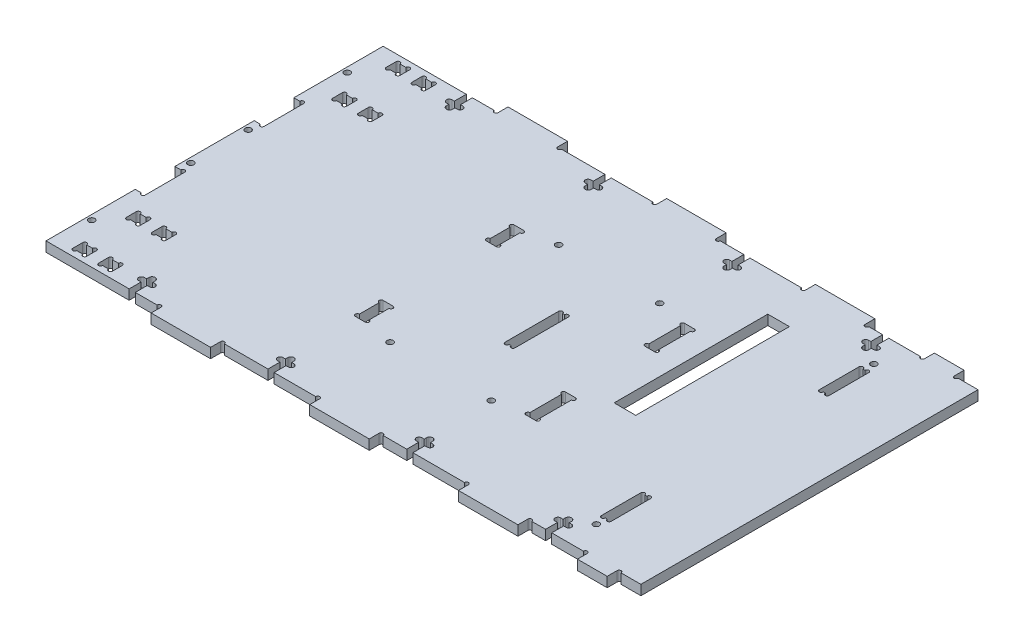
SolidWorks part; units mm, degrees
ref_plane "정면" through (0, 0, 0) normal (0, 0, 1) x (1, 0, 0)
ref_plane "윗면" through (0, 0, 0) normal (0, 1, 0) x (1, 0, 0)
ref_plane "우측면" through (0, 0, 0) normal (1, 0, 0) x (0, 0, -1)
sketch "스케치1" plane through (0, 0, 0) normal (0, 1, 0) x (1, 0, 0)
  line L1 (0, 0) -> (300, 0)
  line L2 (0, 0) -> (0, 170)
  line L3 (0, 170) -> (300, 170)
  line L4 (300, 0) -> (300, 170)
  dimension "D1" = 170
  dimension "D2" = 300
extrude "보스-돌출1" add sketch "스케치1" along normal blind 5
sketch "스케치2" plane through (0, 0, 0) normal (0, -1, 0) x (1, 0, 0)
  line L0 (160, -71.5) -> (160, 0) construction
  line L1 (160, -71.5) -> (165, -71.5)
  line L2 (160, -71.5) -> (160, -98.5)
  line L3 (160, -98.5) -> (165, -98.5)
  line L4 (165, -71.5) -> (165, -98.5)
  line L5 (0, 0) -> (300, 0) construction
  line L6 (160, -98.5) -> (160, -170) construction
  line L7 (300, -170) -> (0, -170) construction
  line L10 (300, 0) -> (300, -170) construction
  line L11 (260, 0) -> (260, -20) construction
  line L12 (260, -20) -> (265, -20)
  line L13 (260, -20) -> (260, -40)
  line L14 (260, -40) -> (265, -40)
  line L15 (265, -20) -> (265, -40)
  line L16 (260, -130) -> (265, -130)
  line L17 (260, -130) -> (260, -150)
  line L18 (260, -150) -> (265, -150)
  line L19 (265, -130) -> (265, -150)
  line L20 (260, -40) -> (260, -130) construction
  line L21 (260, -150) -> (260, -170) construction
  line L22 (265, -130) -> (265, -40) construction
  dimension "D1" = 27
  dimension "D2" = 140
  dimension "D3" = 5
  dimension "D4" = 20
  dimension "D5" = 20
  dimension "D6" = 40
  dimension "D7" = 5
extrude "컷-돌출1" cut sketch "스케치2" against normal blind 10
sketch "스케치3" plane through (0, 5, 0) normal (0, 1, 0) x (1, 0, 0)
  line L0 (183.55, 42.5) -> (180.45, 42.5) construction
  line L1 (183.55, 40) -> (183.55, 45) construction
  line L2 (180.45, 40) -> (180.45, 45) construction
  line L3 (180.45, 42.5) -> (132.55, 42.5) construction
  line L4 (132.55, 40) -> (132.55, 45) construction
  line L5 (132.55, 42.5) -> (129.45, 42.5) construction
  line L6 (129.45, 40) -> (129.45, 45) construction
  line L7 (183.55, 127.5) -> (180.45, 127.5) construction
  line L8 (183.55, 125) -> (183.55, 130) construction
  line L9 (180.45, 125) -> (180.45, 130) construction
  line L10 (180.45, 127.5) -> (132.55, 127.5) construction
  line L11 (132.55, 125) -> (132.55, 130) construction
  line L12 (132.55, 127.5) -> (129.45, 127.5) construction
  line L13 (129.45, 125) -> (129.45, 130) construction
  line L15 (2.5, 101) -> (2.5, 97.9) construction
  line L17 (5, 101) -> (0, 101) construction
  line L18 (262.5, 16.55) -> (262.5, 13.45) construction
  line L19 (265, 16.55) -> (260, 16.55) construction
  line L20 (265, 13.45) -> (260, 13.45) construction
  line L25 (262.5, 156.55) -> (262.5, 153.45) construction
  line L26 (265, 156.55) -> (260, 156.55) construction
  line L27 (265, 153.45) -> (260, 153.45) construction
  line L28 (5, 97.9) -> (0, 97.9) construction
  line L31 (2.5, 151) -> (2.5, 147.9) construction
  line L34 (2.5, 22.1) -> (2.5, 19) construction
  line L35 (5, 22.1) -> (0, 22.1) construction
  line L36 (5, 19) -> (0, 19) construction
  line L37 (2.5, 72.1) -> (2.5, 69) construction
  line L38 (5, 72.1) -> (0, 72.1) construction
  line L39 (5, 69) -> (0, 69) construction
  line L40 (5, 151) -> (0, 151) construction
  line L41 (5, 147.9) -> (0, 147.9) construction
  circle A0 centre (131, 127.5) radius 1.55
  circle A1 centre (182, 127.5) radius 1.55
  circle A2 centre (182, 42.5) radius 1.55
  circle A3 centre (131, 42.5) radius 1.55
  circle A4 centre (2.5, 70.55) radius 1.55
  circle A5 centre (2.5, 20.55) radius 1.55
  circle A6 centre (2.5, 99.45) radius 1.55
  circle A7 centre (2.5, 149.45) radius 1.55
  circle A8 centre (262.5, 155) radius 1.55
  circle A10 centre (262.5, 15) radius 1.55
  dimension "D1" = 3.1
extrude "컷-돌출2" cut sketch "스케치3" against normal blind 10
sketch "스케치4" plane through (0, 0, 0) normal (0, -1, 0) x (1, 0, 0)
  line L1 (0, -125) -> (5, -125)
  line L2 (0, -125) -> (0, -105)
  line L3 (0, -105) -> (5, -105)
  line L4 (5, -125) -> (5, -105)
  line L5 (0, -65) -> (5, -65)
  line L6 (0, -65) -> (0, -45)
  line L7 (0, -45) -> (5, -45)
  line L8 (5, -65) -> (5, -45)
extrude "컷-돌출3" cut sketch "스케치4" against normal blind 5
sketch "스케치5" plane through (0, 0, 0) normal (0, -1, 0) x (1, 0, 0)
  line L2 (5, -45) -> (0, -45) construction
  line L3 (0, -65) -> (5, -65) construction
  line L4 (5, -105) -> (0, -105) construction
  line L5 (0, -125) -> (5, -125) construction
  line L6 (160, -98.5) -> (165, -98.5) construction
  line L7 (165, -71.5) -> (160, -71.5) construction
  line L8 (265, -20) -> (260, -20) construction
  line L9 (260, -40) -> (265, -40) construction
  line L10 (265, -130) -> (260, -130) construction
  line L11 (260, -150) -> (265, -150) construction
  circle A1 centre (4, -45) radius 1
  circle A2 centre (4, -65) radius 1
  circle A5 centre (4, -105) radius 1
  circle A6 centre (4, -125) radius 1
  circle A8 centre (164, -98.5) radius 1
  circle A9 centre (161, -98.5) radius 1
  circle A10 centre (164, -71.5) radius 1
  circle A11 centre (161, -71.5) radius 1
  circle A12 centre (264, -20) radius 1
  circle A13 centre (261, -20) radius 1
  circle A14 centre (264, -40) radius 1
  circle A15 centre (261, -40) radius 1
  circle A16 centre (264, -130) radius 1
  circle A17 centre (261, -130) radius 1
  circle A18 centre (264, -150) radius 1
  circle A19 centre (261, -150) radius 1
  dimension "D1" = 2
extrude "컷-돌출4" cut sketch "스케치5" against normal blind 10
sketch "스케치8" plane through (0, 0, 0) normal (0, -1, 0) x (1, 0, 0)
  line L0 (0, 0) -> (300, 0) construction
  line L1 (58, 0) -> (88, 0)
  line L2 (58, 0) -> (58, 5)
  line L3 (58, 5) -> (88, 5)
  line L4 (88, 0) -> (88, 5)
  line L5 (0, 5) -> (58, 5) construction
  line L6 (0, 0) -> (300, 0) construction
  line L7 (138, 5) -> (168, 5)
  line L8 (138, 5) -> (138, 0)
  line L9 (138, 0) -> (168, 0)
  line L10 (168, 5) -> (168, 0)
  line L11 (0, 0) -> (300, 0) construction
  line L12 (213, 5) -> (243, 5)
  line L13 (213, 5) -> (213, 0)
  line L14 (213, 0) -> (243, 0)
  line L15 (243, 5) -> (243, 0)
  line L16 (0, 0) -> (300, 0) construction
  line L17 (273, 5) -> (288, 5)
  line L18 (273, 5) -> (273, 0)
  line L19 (273, 0) -> (288, 0)
  line L20 (288, 5) -> (288, 0)
  line L21 (300, 0) -> (300, -170) construction
  line L22 (0, -85) -> (300, -85) construction
  line L23 (0, -105) -> (0, -65) construction
  line L24 (288, -175) -> (288, -170)
  line L25 (273, -170) -> (288, -170)
  line L26 (273, -175) -> (273, -170)
  line L27 (273, -175) -> (288, -175)
  line L28 (243, -175) -> (243, -170)
  line L29 (213, -170) -> (243, -170)
  line L30 (213, -175) -> (213, -170)
  line L31 (213, -175) -> (243, -175)
  line L32 (168, -175) -> (168, -170)
  line L33 (138, -170) -> (168, -170)
  line L34 (138, -175) -> (138, -170)
  line L35 (138, -175) -> (168, -175)
  line L36 (88, -170) -> (88, -175)
  line L37 (58, -175) -> (88, -175)
  line L38 (58, -170) -> (58, -175)
  line L39 (58, -170) -> (88, -170)
  dimension "D1" = 12
  dimension "D2" = 15
  dimension "D3" = 30
  dimension "D4" = 30
  dimension "D5" = 45
  dimension "D6" = 30
  dimension "D7" = 50
  dimension "D8" = 30
extrude "보스-돌출2" add sketch "스케치8" against normal blind 5
sketch "스케치9" plane through (0, 0, 0) normal (0, -1, 0) x (1, 0, 0)
  line L0 (0, 0) -> (58, 0) construction
  line L1 (88, 0) -> (138, 0) construction
  line L2 (88, 0) -> (138, 0) construction
  line L3 (168, 0) -> (213, 0) construction
  line L4 (168, 0) -> (213, 0) construction
  line L5 (243, 0) -> (273, 0) construction
  line L6 (243, 0) -> (273, 0) construction
  line L7 (288, 0) -> (300, 0) construction
  line L8 (0, -85) -> (300, -85) construction
  line L9 (0, -105) -> (0, -65) construction
  line L10 (300, 0) -> (300, -170) construction
  circle A0 centre (57, 0) radius 1
  circle A1 centre (89, 0) radius 1
  circle A2 centre (137, 0) radius 1
  circle A3 centre (169, 0) radius 1
  circle A4 centre (212, 0) radius 1
  circle A5 centre (272, 0) radius 1
  circle A6 centre (244, 0) radius 1
  circle A7 centre (289, 0) radius 1
  circle A8 centre (289, -170) radius 1
  circle A9 centre (244, -170) radius 1
  circle A10 centre (272, -170) radius 1
  circle A11 centre (212, -170) radius 1
  circle A12 centre (169, -170) radius 1
  circle A13 centre (137, -170) radius 1
  circle A14 centre (89, -170) radius 1
  circle A15 centre (57, -170) radius 1
  dimension "D1" = 2
extrude "컷-돌출6" cut sketch "스케치9" against normal blind 5
sketch "스케치13" plane through (0, 5, 0) normal (0, 1, 0) x (1, 0, 0)
  line L0 (30, 8.5) -> (30, 30.5) construction
  line L1 (30, 8.5) -> (23, 8.5)
  line L2 (30, 8.5) -> (30, 3.5)
  line L3 (30, 3.5) -> (23, 3.5)
  line L4 (23, 8.5) -> (23, 3.5)
  line L5 (17, 8.5) -> (10, 8.5)
  line L6 (17, 8.5) -> (17, 3.5)
  line L7 (17, 3.5) -> (10, 3.5)
  line L8 (10, 8.5) -> (10, 3.5)
  line L9 (30, 19.5) -> (11.9274, 19.5) construction
  line L10 (10, 30.5) -> (10, 35.5)
  line L11 (17, 35.5) -> (10, 35.5)
  line L12 (17, 30.5) -> (17, 35.5)
  line L13 (17, 30.5) -> (10, 30.5)
  line L14 (23, 30.5) -> (23, 35.5)
  line L15 (30, 35.5) -> (23, 35.5)
  line L16 (30, 30.5) -> (30, 35.5)
  line L17 (30, 30.5) -> (23, 30.5)
  line L18 (0, 85) -> (49.672, 85) construction
  line L19 (0, 105) -> (0, 65) construction
  line L20 (30, 150.5) -> (11.9274, 150.5) construction
  line L21 (30, 161.5) -> (30, 139.5) construction
  line L22 (30, 139.5) -> (23, 139.5)
  line L23 (30, 139.5) -> (30, 134.5)
  line L24 (30, 134.5) -> (23, 134.5)
  line L25 (23, 139.5) -> (23, 134.5)
  line L26 (17, 139.5) -> (10, 139.5)
  line L27 (17, 139.5) -> (17, 134.5)
  line L28 (17, 134.5) -> (10, 134.5)
  line L29 (10, 139.5) -> (10, 134.5)
  line L30 (10, 161.5) -> (10, 166.5)
  line L31 (17, 166.5) -> (10, 166.5)
  line L32 (17, 161.5) -> (17, 166.5)
  line L33 (17, 161.5) -> (10, 161.5)
  line L34 (23, 161.5) -> (23, 166.5)
  line L35 (30, 166.5) -> (23, 166.5)
  line L36 (30, 161.5) -> (30, 166.5)
  line L37 (30, 161.5) -> (23, 161.5)
extrude "컷-돌출9" cut sketch "스케치13" against normal blind 10
sketch "스케치14" plane through (0, 0, 0) normal (0, -1, 0) x (1, 0, 0)
  line L0 (10, -8.5) -> (17, -8.5) construction
  line L1 (17, -3.5) -> (10, -3.5) construction
  line L2 (17, -30.5) -> (23, -30.5) construction
  line L3 (23, -30.5) -> (23, -8.5) construction
  line L4 (23, -8.5) -> (17, -8.5) construction
  line L5 (17, -8.5) -> (17, -30.5) construction
  line L6 (20, -30.5) -> (20, -8.5) construction
  line L7 (17, -19.5) -> (23, -19.5) construction
  line L8 (0, -85) -> (55.1733, -85) construction
  line L9 (0, -105) -> (0, -65) construction
  line L10 (17, -150.5) -> (23, -150.5) construction
  line L11 (20, -139.5) -> (20, -161.5) construction
  line L12 (17, -161.5) -> (17, -139.5) construction
  line L13 (23, -161.5) -> (17, -161.5) construction
  line L14 (23, -139.5) -> (23, -161.5) construction
  line L15 (17, -139.5) -> (23, -139.5) construction
  circle A0 centre (11, -8.5) radius 1
  circle A1 centre (11, -3.5) radius 1
  circle A2 centre (16, -3.5) radius 1
  circle A3 centre (16, -8.5) radius 1
  circle A4 centre (24, -8.5) radius 1
  circle A5 centre (24, -3.5) radius 1
  circle A6 centre (29, -3.5) radius 1
  circle A7 centre (29, -8.5) radius 1
  circle A8 centre (29, -30.5) radius 1
  circle A9 centre (29, -35.5) radius 1
  circle A10 centre (24, -35.5) radius 1
  circle A11 centre (24, -30.5) radius 1
  circle A12 centre (16, -30.5) radius 1
  circle A13 centre (16, -35.5) radius 1
  circle A14 centre (11, -35.5) radius 1
  circle A15 centre (11, -30.5) radius 1
  circle A16 centre (11, -139.5) radius 1
  circle A17 centre (11, -134.5) radius 1
  circle A18 centre (16, -134.5) radius 1
  circle A19 centre (16, -139.5) radius 1
  circle A20 centre (24, -139.5) radius 1
  circle A21 centre (24, -134.5) radius 1
  circle A22 centre (29, -134.5) radius 1
  circle A23 centre (29, -139.5) radius 1
  circle A24 centre (29, -161.5) radius 1
  circle A25 centre (29, -166.5) radius 1
  circle A26 centre (24, -166.5) radius 1
  circle A27 centre (24, -161.5) radius 1
  circle A28 centre (16, -161.5) radius 1
  circle A29 centre (16, -166.5) radius 1
  circle A30 centre (11, -166.5) radius 1
  circle A31 centre (11, -161.5) radius 1
  dimension "D1" = 2
extrude "컷-돌출10" cut sketch "스케치14" against normal blind 10
sketch "스케치15" plane through (0, 5, 0) normal (0, 1, 0) x (1, 0, 0)
  line L1 (111, 125) -> (116, 125)
  line L2 (111, 125) -> (111, 111)
  line L3 (111, 111) -> (116, 111)
  line L4 (116, 125) -> (116, 111)
  line L5 (111, 45) -> (116, 45)
  line L6 (111, 45) -> (111, 59)
  line L7 (111, 59) -> (116, 59)
  line L8 (116, 45) -> (116, 59)
  line L9 (197, 65) -> (202, 65)
  line L10 (197, 65) -> (197, 45)
  line L11 (197, 45) -> (202, 45)
  line L12 (202, 65) -> (202, 45)
  line L13 (197, 105) -> (202, 105)
  line L14 (197, 105) -> (197, 125)
  line L15 (197, 125) -> (202, 125)
  line L16 (202, 105) -> (202, 125)
  arc A0 (116, 56.5) -> (116, 59) centre (116, 57.75) ccw construction
  dimension "D1" = 5
extrude "컷-돌출11" cut sketch "스케치15" against normal blind 10
sketch "스케치16" plane through (0, 5, 0) normal (0, 1, 0) x (1, 0, 0)
  line L0 (111, 59) -> (111, 45) construction
  line L1 (116, 45) -> (116, 59) construction
  line L2 (111, 125) -> (111, 111) construction
  line L3 (116, 111) -> (116, 125) construction
  line L4 (202, 105) -> (202, 125) construction
  line L5 (197, 125) -> (197, 105) construction
  line L6 (197, 65) -> (197, 45) construction
  line L7 (202, 45) -> (202, 65) construction
  circle A0 centre (111, 46) radius 1
  circle A1 centre (116, 46) radius 1
  circle A2 centre (116, 58) radius 1
  circle A3 centre (111, 58) radius 1
  circle A4 centre (111, 112) radius 1
  circle A5 centre (116, 112) radius 1
  circle A6 centre (116, 124) radius 1
  circle A7 centre (111, 124) radius 1
  circle A8 centre (202, 124) radius 1
  circle A10 centre (197, 124) radius 1
  circle A11 centre (197, 64) radius 1
  circle A12 centre (202, 64) radius 1
  circle A13 centre (202, 106) radius 1
  circle A14 centre (197, 106) radius 1
  circle A15 centre (197, 46) radius 1
  circle A16 centre (202, 46) radius 1
  dimension "D1" = 2
extrude "컷-돌출12" cut sketch "스케치16" against normal blind 10
sketch "스케치17" plane through (0, 5, 0) normal (0, 1, 0) x (1, 0, 0)
  line L0 (219, 97.5569) -> (219, 95.1974) construction
  line L1 (214, 72.5) -> (224.9, 72.5)
  line L2 (214, 72.5) -> (214, 150)
  line L3 (214, 150) -> (224.9, 150)
  line L4 (224.9, 72.5) -> (224.9, 150)
  line L6 (219.9, 97.5569) -> (219.9, 95.1974) construction
  line L7 (2.5, -7.5) -> (297.5, -7.5) construction
  line L8 (211, 170) -> (170, 170) construction
  dimension "D1" = 5
  dimension "D2" = 5
  dimension "D3" = 80
  dimension "D4" = 20
extrude "컷-돌출13" cut sketch "스케치17" against normal blind 10
sketch "스케치7" plane through (0, 0, 0) normal (0, -1, 0) x (1, 0, 0)
  line L0 (115.0287, -170) -> (111.9287, -170)
  line L1 (115.0287, -164) -> (116.2287, -164)
  line L2 (115.0287, -161.2) -> (115.0287, -160)
  line L3 (111.9287, -161.2) -> (111.9287, -160)
  line L4 (111.9287, -161.2) -> (110.7287, -161.2)
  line L5 (111.9287, -170) -> (111.9287, -164)
  line L6 (110.7287, -164) -> (111.9287, -164)
  line L7 (115.0287, -170) -> (115.0287, -164)
  line L8 (116.2287, -161.2) -> (115.0287, -161.2)
  line L9 (115.0287, -161.2) -> (111.9287, -161.2) construction
  line L10 (115.0287, -161.2) -> (115.0287, -164) construction
  line L11 (111.9287, -164) -> (111.9287, -161.2) construction
  line L12 (115.0287, -160) -> (111.9287, -160) construction
  line L13 (113.4787, -160) -> (113.4787, -157.529) construction
  line L14 (110.7287, -161.2) -> (110.7287, -164) construction
  line L15 (116.2287, -164) -> (116.2287, -161.2) construction
  line L16 (115.0287, -164) -> (111.9287, -164) construction
  line L17 (185.0287, -170) -> (181.9287, -170)
  line L18 (185.0287, -164) -> (186.2287, -164)
  line L19 (185.0287, -161.2) -> (185.0287, -160)
  line L20 (181.9287, -161.2) -> (181.9287, -160)
  line L21 (181.9287, -161.2) -> (180.7287, -161.2)
  line L22 (181.9287, -170) -> (181.9287, -164)
  line L23 (180.7287, -164) -> (181.9287, -164)
  line L24 (185.0287, -170) -> (185.0287, -164)
  line L25 (186.2287, -161.2) -> (185.0287, -161.2)
  line L26 (185.0287, -161.2) -> (181.9287, -161.2) construction
  line L27 (185.0287, -161.2) -> (185.0287, -164) construction
  line L28 (181.9287, -164) -> (181.9287, -161.2) construction
  line L29 (185.0287, -160) -> (181.9287, -160) construction
  line L30 (45.0287, -161.2) -> (41.9287, -161.2) construction
  line L31 (45.0287, -161.2) -> (45.0287, -164) construction
  line L32 (41.9287, -164) -> (41.9287, -161.2) construction
  line L33 (45.0287, -160) -> (41.9287, -160) construction
  line L34 (43.4787, -160) -> (43.4787, -157.529) construction
  line L35 (183.4787, -160) -> (183.4787, -157.529) construction
  line L36 (180.7287, -161.2) -> (180.7287, -164) construction
  line L37 (186.2287, -164) -> (186.2287, -161.2) construction
  line L38 (185.0287, -164) -> (181.9287, -164) construction
  line L39 (255.0287, -170) -> (251.9287, -170)
  line L40 (255.0287, -164) -> (256.2287, -164)
  line L41 (255.0287, -161.2) -> (255.0287, -160)
  line L42 (251.9287, -161.2) -> (251.9287, -160)
  line L43 (251.9287, -161.2) -> (250.7287, -161.2)
  line L44 (251.9287, -170) -> (251.9287, -164)
  line L45 (250.7287, -164) -> (251.9287, -164)
  line L46 (255.0287, -170) -> (255.0287, -164)
  line L47 (256.2287, -161.2) -> (255.0287, -161.2)
  line L48 (255.0287, -161.2) -> (251.9287, -161.2) construction
  line L49 (255.0287, -161.2) -> (255.0287, -164) construction
  line L50 (251.9287, -164) -> (251.9287, -161.2) construction
  line L51 (255.0287, -160) -> (251.9287, -160) construction
  line L52 (253.4787, -160) -> (253.4787, -157.529) construction
  line L53 (250.7287, -161.2) -> (250.7287, -164) construction
  line L54 (256.2287, -164) -> (256.2287, -161.2) construction
  line L55 (255.0287, -164) -> (251.9287, -164) construction
  line L56 (45.0287, -6) -> (41.9287, -6) construction
  line L57 (46.2287, -6) -> (46.2287, -8.8) construction
  line L58 (40.7287, -8.8) -> (40.7287, -6) construction
  line L59 (255.0287, -6) -> (251.9287, -6) construction
  line L60 (256.2287, -6) -> (256.2287, -8.8) construction
  line L61 (250.7287, -8.8) -> (250.7287, -6) construction
  line L62 (253.4787, -10) -> (253.4787, -12.471) construction
  line L63 (255.0287, -10) -> (251.9287, -10) construction
  line L64 (251.9287, -6) -> (251.9287, -8.8) construction
  line L65 (255.0287, -8.8) -> (255.0287, -6) construction
  line L66 (255.0287, -8.8) -> (251.9287, -8.8) construction
  line L67 (185.0287, -6) -> (181.9287, -6) construction
  line L68 (186.2287, -6) -> (186.2287, -8.8) construction
  line L69 (40.7287, -161.2) -> (40.7287, -164) construction
  line L71 (180.7287, -8.8) -> (180.7287, -6) construction
  line L72 (183.4787, -10) -> (183.4787, -12.471) construction
  line L73 (43.4787, -10) -> (43.4787, -12.471) construction
  line L74 (45.0287, -10) -> (41.9287, -10) construction
  line L75 (0, -85) -> (300, -85) construction
  line L76 (0, -105) -> (0, -65) construction
  line L77 (300, 0) -> (300, -170) construction
  line L78 (46.2287, -164) -> (46.2287, -161.2) construction
  line L79 (45.0287, -164) -> (41.9287, -164) construction
  line L80 (41.9287, -6) -> (41.9287, -8.8) construction
  line L81 (45.0287, -8.8) -> (45.0287, -6) construction
  line L82 (45.0287, -8.8) -> (41.9287, -8.8) construction
  line L83 (185.0287, -10) -> (181.9287, -10) construction
  line L84 (181.9287, -6) -> (181.9287, -8.8) construction
  line L85 (185.0287, -8.8) -> (185.0287, -6) construction
  line L86 (185.0287, -8.8) -> (181.9287, -8.8) construction
  line L87 (115.0287, -6) -> (111.9287, -6) construction
  line L88 (116.2287, -6) -> (116.2287, -8.8) construction
  line L89 (110.7287, -8.8) -> (110.7287, -6) construction
  line L90 (113.4787, -10) -> (113.4787, -12.471) construction
  line L91 (115.0287, -10) -> (111.9287, -10) construction
  line L92 (111.9287, -6) -> (111.9287, -8.8) construction
  line L93 (115.0287, -8.8) -> (115.0287, -6) construction
  line L94 (115.0287, -8.8) -> (111.9287, -8.8) construction
  line L95 (46.2287, -8.8) -> (45.0287, -8.8)
  line L96 (45.0287, 0) -> (45.0287, -6)
  line L97 (45.0287, -170) -> (41.9287, -170)
  line L98 (45.0287, -164) -> (46.2287, -164)
  line L99 (45.0287, -161.2) -> (45.0287, -160)
  line L100 (41.9287, -161.2) -> (41.9287, -160)
  line L101 (41.9287, -161.2) -> (40.7287, -161.2)
  line L102 (41.9287, -170) -> (41.9287, -164)
  line L103 (40.7287, -164) -> (41.9287, -164)
  line L104 (45.0287, -170) -> (45.0287, -164)
  line L105 (46.2287, -161.2) -> (45.0287, -161.2)
  line L106 (325.0287, -170) -> (321.9287, -170) [skipped]
  line L107 (325.0287, -164) -> (326.2287, -164) [skipped]
  line L108 (325.0287, -161.2) -> (325.0287, -160) [skipped]
  line L109 (321.9287, -161.2) -> (321.9287, -160) [skipped]
  line L110 (321.9287, -161.2) -> (320.7287, -161.2) [skipped]
  line L111 (321.9287, -170) -> (321.9287, -164) [skipped]
  line L112 (320.7287, -164) -> (321.9287, -164) [skipped]
  line L113 (325.0287, -170) -> (325.0287, -164) [skipped]
  line L114 (326.2287, -161.2) -> (325.0287, -161.2) [skipped]
  line L115 (325.0287, -161.2) -> (321.9287, -161.2) construction
  line L116 (325.0287, -161.2) -> (325.0287, -164) construction
  line L117 (321.9287, -164) -> (321.9287, -161.2) construction
  line L118 (325.0287, -160) -> (321.9287, -160) construction
  line L119 (323.4787, -160) -> (323.4787, -157.529) construction
  line L120 (320.7287, -161.2) -> (320.7287, -164) construction
  line L121 (326.2287, -164) -> (326.2287, -161.2) construction
  line L122 (325.0287, -164) -> (321.9287, -164) construction
  line L123 (40.7287, -6) -> (41.9287, -6)
  line L124 (41.9287, 0) -> (41.9287, -6)
  line L125 (41.9287, -8.8) -> (40.7287, -8.8)
  line L126 (41.9287, -8.8) -> (41.9287, -10)
  line L127 (45.0287, -8.8) -> (45.0287, -10)
  line L128 (45.0287, -6) -> (46.2287, -6)
  line L129 (45.0287, 0) -> (41.9287, 0)
  line L130 (256.2287, -8.8) -> (255.0287, -8.8)
  line L131 (255.0287, 0) -> (255.0287, -6)
  line L132 (250.7287, -6) -> (251.9287, -6)
  line L133 (251.9287, 0) -> (251.9287, -6)
  line L134 (251.9287, -8.8) -> (250.7287, -8.8)
  line L135 (251.9287, -8.8) -> (251.9287, -10)
  line L136 (255.0287, -8.8) -> (255.0287, -10)
  line L137 (255.0287, -6) -> (256.2287, -6)
  line L138 (255.0287, 0) -> (251.9287, 0)
  line L139 (186.2287, -8.8) -> (185.0287, -8.8)
  line L140 (185.0287, 0) -> (185.0287, -6)
  line L141 (180.7287, -6) -> (181.9287, -6)
  line L142 (181.9287, 0) -> (181.9287, -6)
  line L143 (181.9287, -8.8) -> (180.7287, -8.8)
  line L144 (181.9287, -8.8) -> (181.9287, -10)
  line L145 (185.0287, -8.8) -> (185.0287, -10)
  line L146 (185.0287, -6) -> (186.2287, -6)
  line L147 (185.0287, 0) -> (181.9287, 0)
  line L148 (116.2287, -8.8) -> (115.0287, -8.8)
  line L149 (115.0287, 0) -> (115.0287, -6)
  line L150 (110.7287, -6) -> (111.9287, -6)
  line L151 (111.9287, 0) -> (111.9287, -6)
  line L152 (111.9287, -8.8) -> (110.7287, -8.8)
  line L153 (111.9287, -8.8) -> (111.9287, -10)
  line L154 (115.0287, -8.8) -> (115.0287, -10)
  line L155 (115.0287, -6) -> (116.2287, -6)
  line L156 (115.0287, 0) -> (111.9287, 0)
  arc A0 (111.9287, -160) -> (115.0287, -160) centre (113.4787, -160) cw
  arc A1 (116.2287, -161.2) -> (116.2287, -164) centre (116.2287, -162.6) cw
  arc A2 (110.7287, -164) -> (110.7287, -161.2) centre (110.7287, -162.6) cw
  arc A3 (181.9287, -160) -> (185.0287, -160) centre (183.4787, -160) cw
  arc A4 (186.2287, -161.2) -> (186.2287, -164) centre (186.2287, -162.6) cw
  arc A5 (180.7287, -164) -> (180.7287, -161.2) centre (180.7287, -162.6) cw
  arc A6 (251.9287, -160) -> (255.0287, -160) centre (253.4787, -160) cw
  arc A7 (256.2287, -161.2) -> (256.2287, -164) centre (256.2287, -162.6) cw
  arc A8 (250.7287, -164) -> (250.7287, -161.2) centre (250.7287, -162.6) cw
  arc A9 (40.7287, -6) -> (40.7287, -8.8) centre (40.7287, -7.4) ccw
  arc A10 (46.2287, -8.8) -> (46.2287, -6) centre (46.2287, -7.4) ccw
  arc A11 (41.9287, -10) -> (45.0287, -10) centre (43.4787, -10) ccw
  arc A12 (250.7287, -6) -> (250.7287, -8.8) centre (250.7287, -7.4) ccw
  arc A13 (41.9287, -160) -> (45.0287, -160) centre (43.4787, -160) cw
  arc A14 (46.2287, -161.2) -> (46.2287, -164) centre (46.2287, -162.6) cw
  arc A15 (40.7287, -164) -> (40.7287, -161.2) centre (40.7287, -162.6) cw
  arc A16 (321.9287, -160) -> (325.0287, -160) centre (323.4787, -160) cw [skipped]
  arc A17 (326.2287, -161.2) -> (326.2287, -164) centre (326.2287, -162.6) cw [skipped]
  arc A18 (320.7287, -164) -> (320.7287, -161.2) centre (320.7287, -162.6) cw [skipped]
  arc A19 (256.2287, -8.8) -> (256.2287, -6) centre (256.2287, -7.4) ccw
  arc A20 (251.9287, -10) -> (255.0287, -10) centre (253.4787, -10) ccw
  arc A21 (180.7287, -6) -> (180.7287, -8.8) centre (180.7287, -7.4) ccw
  arc A22 (186.2287, -8.8) -> (186.2287, -6) centre (186.2287, -7.4) ccw
  arc A23 (181.9287, -10) -> (185.0287, -10) centre (183.4787, -10) ccw
  arc A24 (110.7287, -6) -> (110.7287, -8.8) centre (110.7287, -7.4) ccw
  arc A25 (116.2287, -8.8) -> (116.2287, -6) centre (116.2287, -7.4) ccw
  arc A26 (111.9287, -10) -> (115.0287, -10) centre (113.4787, -10) ccw
  dimension "D1" = 5
extrude "컷-돌출5" cut sketch "스케치7" against normal blind 10
sketch "스케치18" plane through (0, 0, 0) normal (0, -1, 0) x (1, 0, 0)
  line L0 (0, -85) -> (300, -85) construction
  line L1 (0, -105) -> (0, -65) construction
  line L2 (300, 0) -> (300, -170) construction
  line L4 (285, -152.5) -> (15, -152.5) construction
  line L5 (285, -152.5) -> (285, -17.5) construction
  line L6 (285, -17.5) -> (15, -17.5) construction
  line L7 (15, -152.5) -> (15, -17.5) construction
  line L8 (285, -152.5) -> (15, -17.5) construction
  line L9 (285, -17.5) -> (15, -152.5) construction
  circle A0 centre (15, -17.5) radius 6
  circle A1 centre (15, -152.5) radius 6
  circle A2 centre (285, -17.5) radius 6
  circle A3 centre (285, -152.5) radius 6
  point P6 (150, -85)
  dimension "D3" = 12
  dimension "D1" = 135
  dimension "D2" = 270
extrude "컷-돌출14" cut sketch "스케치18" against normal blind 1.5
